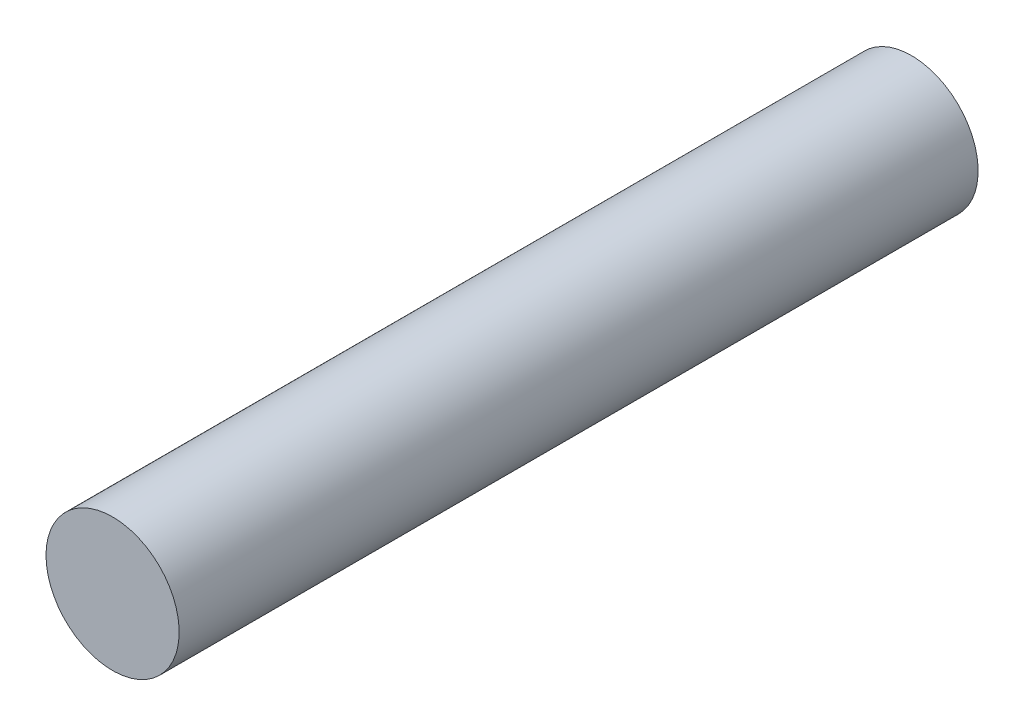
SolidWorks part; units mm, degrees
ref_plane "Front Plane" through (0, 0, 0) normal (0, 0, 1) x (1, 0, 0)
ref_plane "Top Plane" through (0, 0, 0) normal (0, 1, 0) x (1, 0, 0)
ref_plane "Right Plane" through (0, 0, 0) normal (1, 0, 0) x (0, 0, -1)
sketch "Sketch1" plane through (0, 0, 0) normal (0, 0, 1) x (1, 0, 0)
  circle A0 centre (0, 0) radius 3.175
  dimension "D1" = 6.35
extrude "Boss-Extrude1" add sketch "Sketch1" along normal mid plane 38.1
